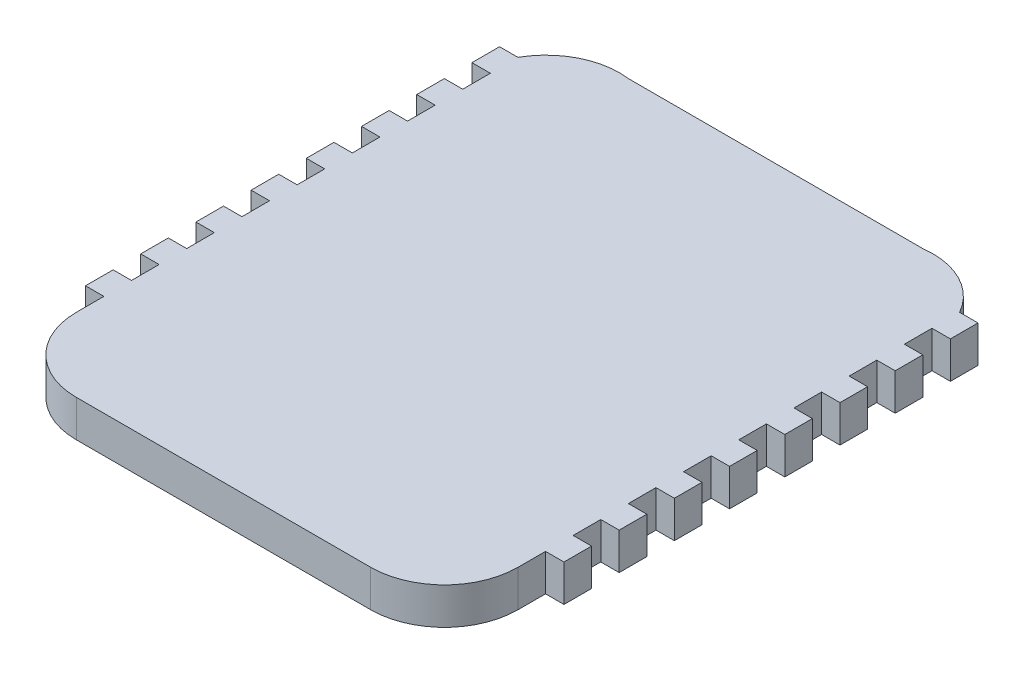
SolidWorks part; units mm, degrees
ref_plane "Front Plane" through (0, 0, 0) normal (0, 0, 1) x (1, 0, 0)
ref_plane "Top Plane" through (0, 0, 0) normal (0, 1, 0) x (1, 0, 0)
ref_plane "Right Plane" through (0, 0, 0) normal (1, 0, 0) x (0, 0, -1)
sketch "Sketch1" plane through (0, 0, 0) normal (0, 1, 0) x (1, 0, 0)
  line L0 (363.0116, 530.3309) -> (1607.4617, 530.3309) construction
  line L1 (-10, 30) -> (-10, 270)
  line L6 (30, 290) -> (190, 290)
  line L7 (230, 30) -> (230, 270)
  line L8 (30, -10) -> (190, -10)
  arc A4 (30, 290) -> (-10, 270) centre (24.8324, 250.3352) ccw
  arc A5 (190, 290) -> (230, 270) centre (195.1676, 250.3352) cw
  arc A6 (230, 30) -> (190, -10) centre (190, 30) cw
  arc A7 (-10, 30) -> (30, -10) centre (30, 30) ccw
  point P13 (220, 0)
  point P16 (0, 0)
  dimension "D3" = 240
  dimension "D1" = 300
  dimension "D2" = 220
extrude "Boss-Extrude1" add sketch "Sketch1" along normal blind 20
sketch "Sketch3" plane through (-10, 0, 0) normal (-1, 0, 0) x (0, 0, 1)
  line L0 (-270, 20) -> (-30, 20) construction
  line L1 (-270, 0) -> (-255, 0)
  line L2 (-270, 0) -> (-270, 20)
  line L3 (-270, 20) -> (-255, 20)
  line L4 (-255, 0) -> (-255, 20)
  line L5 (-255, 0) -> (-255, 20)
  line L6 (-255, 0) -> (-240, 0)
  line L7 (-240, 0) -> (-240, 20)
  line L8 (-255, 20) -> (-240, 20)
  line L9 (-240, 0) -> (-240, 20)
  line L10 (-240, 0) -> (-225, 0)
  line L11 (-225, 0) -> (-225, 20)
  line L12 (-240, 20) -> (-225, 20)
  line L13 (-225, 0) -> (-225, 20)
  line L14 (-225, 0) -> (-210, 0)
  line L15 (-210, 0) -> (-210, 20)
  line L16 (-225, 20) -> (-210, 20)
  line L17 (-210, 0) -> (-210, 20)
  line L18 (-210, 0) -> (-195, 0)
  line L19 (-195, 0) -> (-195, 20)
  line L20 (-210, 20) -> (-195, 20)
  line L21 (-195, 0) -> (-195, 20)
  line L22 (-195, 0) -> (-180, 0)
  line L23 (-180, 0) -> (-180, 20)
  line L24 (-195, 20) -> (-180, 20)
  line L25 (-180, 0) -> (-180, 20)
  line L26 (-180, 0) -> (-165, 0)
  line L27 (-165, 0) -> (-165, 20)
  line L28 (-180, 20) -> (-165, 20)
  line L29 (-165, 0) -> (-165, 20)
  line L30 (-165, 0) -> (-150, 0)
  line L31 (-150, 0) -> (-150, 20)
  line L32 (-165, 20) -> (-150, 20)
  line L33 (-150, 0) -> (-150, 20)
  line L34 (-150, 0) -> (-135, 0)
  line L35 (-135, 0) -> (-135, 20)
  line L36 (-150, 20) -> (-135, 20)
  line L37 (-135, 0) -> (-135, 20)
  line L38 (-135, 0) -> (-120, 0)
  line L39 (-120, 0) -> (-120, 20)
  line L40 (-135, 20) -> (-120, 20)
  line L41 (-120, 0) -> (-120, 20)
  line L42 (-120, 0) -> (-105, 0)
  line L43 (-105, 0) -> (-105, 20)
  line L44 (-120, 20) -> (-105, 20)
  line L45 (-105, 0) -> (-105, 20)
  line L46 (-105, 0) -> (-90, 0)
  line L47 (-90, 0) -> (-90, 20)
  line L48 (-105, 20) -> (-90, 20)
  line L49 (-90, 0) -> (-90, 20)
  line L50 (-90, 0) -> (-75, 0)
  line L51 (-75, 0) -> (-75, 20)
  line L52 (-90, 20) -> (-75, 20)
  line L53 (-75, 0) -> (-75, 20)
  line L54 (-75, 0) -> (-60, 0)
  line L55 (-60, 0) -> (-60, 20)
  line L56 (-75, 20) -> (-60, 20)
  line L57 (-60, 0) -> (-60, 20)
  line L58 (-60, 0) -> (-45, 0)
  line L59 (-45, 0) -> (-45, 20)
  line L60 (-60, 20) -> (-45, 20)
  line L61 (-45, 0) -> (-45, 20)
  line L62 (-45, 0) -> (-30, 0)
  line L63 (-30, 0) -> (-30, 20)
  line L64 (-45, 20) -> (-30, 20)
  line M3 (-270, 0) -> (-30, 0)
  line M5 (-30, 20) -> (-270, 20)
  line M6 (-270, 20) -> (-270, 0)
  dimension "D1" = 15
  dimension "D2" = 16
extrude "Boss-Extrude2" add sketch "Sketch3" along normal blind 10 contours L4 M3 M5 M6 | L11 L7 M3 M5 | L19 L15 M3 M5 | L35 L31 M3 M5 | L43 L39 M3 M5 | L51 L47 M3 M5 | L59 L55 M3 M5 | L27 L28 L25 L26 region at (-10, 10, -262.5) region at (-10, 10, -232.5) region at (-10, 10, -202.5) region at (-10, 10, -142.5) region at (-10, 10, -112.5) region at (-10, 10, -82.5) region at (-10, 10, -52.5)
sketch "Sketch4" plane through (230, 0, 0) normal (1, 0, 0) x (0, 0, -1)
  line L0 (30, 20) -> (270, 20) construction
  line L1 (270, 0) -> (255, 0)
  line L2 (270, 0) -> (270, 20)
  line L3 (270, 20) -> (255, 20)
  line L4 (255, 0) -> (255, 20)
  line L5 (255, 0) -> (255, 20)
  line L6 (255, 0) -> (240, 0)
  line L7 (240, 0) -> (240, 20)
  line L8 (255, 20) -> (240, 20)
  line L9 (240, 0) -> (240, 20)
  line L10 (240, 0) -> (225, 0)
  line L11 (225, 0) -> (225, 20)
  line L12 (240, 20) -> (225, 20)
  line L13 (225, 0) -> (225, 20)
  line L14 (225, 0) -> (210, 0)
  line L15 (210, 0) -> (210, 20)
  line L16 (225, 20) -> (210, 20)
  line L17 (210, 0) -> (210, 20)
  line L18 (210, 0) -> (195, 0)
  line L19 (195, 0) -> (195, 20)
  line L20 (210, 20) -> (195, 20)
  line L21 (195, 0) -> (195, 20)
  line L22 (195, 0) -> (180, 0)
  line L23 (180, 0) -> (180, 20)
  line L24 (195, 20) -> (180, 20)
  line L25 (180, 0) -> (180, 20)
  line L26 (180, 0) -> (165, 0)
  line L27 (165, 0) -> (165, 20)
  line L28 (180, 20) -> (165, 20)
  line L29 (165, 0) -> (165, 20)
  line L30 (165, 0) -> (150, 0)
  line L31 (150, 0) -> (150, 20)
  line L32 (165, 20) -> (150, 20)
  line L33 (150, 0) -> (150, 20)
  line L34 (150, 0) -> (135, 0)
  line L35 (135, 0) -> (135, 20)
  line L36 (150, 20) -> (135, 20)
  line L37 (135, 0) -> (135, 20)
  line L38 (135, 0) -> (120, 0)
  line L39 (120, 0) -> (120, 20)
  line L40 (135, 20) -> (120, 20)
  line L41 (120, 0) -> (120, 20)
  line L42 (120, 0) -> (105, 0)
  line L43 (105, 0) -> (105, 20)
  line L44 (120, 20) -> (105, 20)
  line L45 (105, 0) -> (105, 20)
  line L46 (105, 0) -> (90, 0)
  line L47 (90, 0) -> (90, 20)
  line L48 (105, 20) -> (90, 20)
  line L49 (90, 0) -> (90, 20)
  line L50 (90, 0) -> (75, 0)
  line L51 (75, 0) -> (75, 20)
  line L52 (90, 20) -> (75, 20)
  line L53 (75, 0) -> (75, 20)
  line L54 (75, 0) -> (60, 0)
  line L55 (60, 0) -> (60, 20)
  line L56 (75, 20) -> (60, 20)
  line L57 (60, 0) -> (60, 20)
  line L58 (60, 0) -> (45, 0)
  line L59 (45, 0) -> (45, 20)
  line L60 (60, 20) -> (45, 20)
  line L61 (45, 0) -> (45, 20)
  line L62 (45, 0) -> (30, 0)
  line L63 (30, 0) -> (30, 20)
  line L64 (45, 20) -> (30, 20)
  line M5 (30, 0) -> (270, 0)
  line M6 (270, 0) -> (270, 20)
  line M7 (270, 20) -> (30, 20)
  dimension "D1" = 15
  dimension "D2" = 16
extrude "Boss-Extrude3" add sketch "Sketch4" along normal blind 10 contours L4 M5 M6 M7 | L11 L7 M5 M7 | L27 L23 M5 M7 | L35 L31 M5 M7 | L43 L39 M5 M7 | L51 L47 M5 M7 | L59 L55 M5 M7 | L18 L19 L20 L17 region at (230, 10, -262.5) region at (230, 10, -232.5) region at (230, 10, -172.5) region at (230, 10, -142.5) region at (230, 10, -112.5) region at (230, 10, -82.5) region at (230, 10, -52.5)
